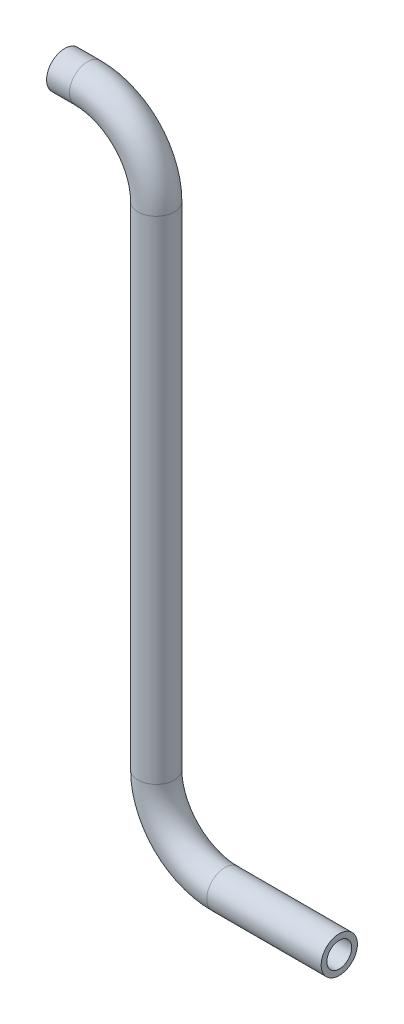
SolidWorks part; units mm, degrees
material "Plain Carbon Steel"
ref_plane "Piano frontale" through (0, 0, 0) normal (0, 0, 1) x (1, 0, 0)
ref_plane "Piano superiore" through (0, 0, 0) normal (0, 1, 0) x (1, 0, 0)
ref_plane "Piano destro" through (0, 0, 0) normal (1, 0, 0) x (0, 0, -1)
sketch "Schizzo1" plane through (0, 0, 0) normal (0, 0, 1) x (1, 0, 0)
  line L0 (0, 6) -> (0, 49)
  line L1 (-6, 55) -> (-8, 55)
  line L2 (6, 0) -> (16, 0)
  line L3 (-8, 57.5593) -> (-8, 77.3397) construction
  arc A0 (0, 49) -> (-6, 55) centre (-6, 49) ccw
  arc A1 (0, 6) -> (6, 0) centre (6, 6) ccw
  point P7 (0, 55)
  point P10 (0, 0)
  dimension "D3" = 6
  dimension "D1" = 55
  dimension "D2" = 10
  dimension "D4" = 90
  dimension "D5" = 90
sweep "Sweep-Sottile1" add path "Schizzo1" circular profile diameter 3.17 parameters "D1"=0.5, "D3"=3.17
